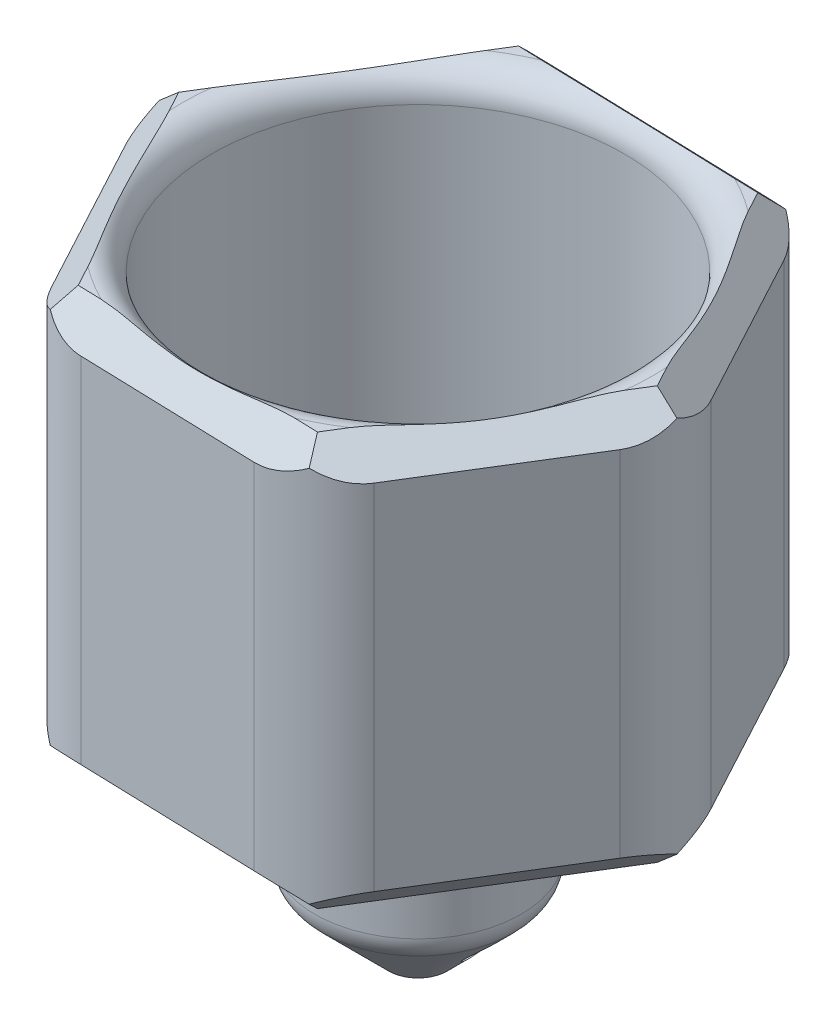
SolidWorks part; units mm, degrees
ref_plane "Front" through (0, 0, 0) normal (0, 0, 1) x (1, 0, 0)
ref_plane "Top" through (0, 0, 0) normal (0, 1, 0) x (1, 0, 0)
ref_plane "Right" through (0, 0, 0) normal (1, 0, 0) x (0, 0, -1)
sketch "Esquisse1" plane through (0, 0, 0) normal (0, 1, 0) x (1, 0, 0)
  line L1 (0.5011, 0.8102) -> (-0.451, 0.8391)
  line L2 (-0.451, 0.8391) -> (-0.9522, 0.0289)
  line L3 (-0.9522, 0.0289) -> (-0.5011, -0.8102)
  line L4 (-0.5011, -0.8102) -> (0.451, -0.8391)
  line L5 (0.451, -0.8391) -> (0.9522, -0.0289)
  line L6 (0.9522, -0.0289) -> (0.5011, 0.8102)
  circle A0 centre (0, 0) radius 0.7
  circle A1 centre (0, 0) radius 0.825 construction
  dimension "D1" = 1.4
  dimension "D2" = 1.65
extrude "Boss.-Extru.1" add sketch "Esquisse1" along normal blind 1.3
sketch "Esquisse2" plane through (0, 0, 0) normal (0, -1, 0) x (1, 0, 0)
  line L6 (0.5011, -0.8102) -> (0.9522, 0.0289)
  line L7 (0.9522, 0.0289) -> (0.451, 0.8391)
  line L8 (0.451, 0.8391) -> (-0.5011, 0.8102)
  line L9 (-0.5011, 0.8102) -> (-0.9522, -0.0289)
  line L10 (-0.9522, -0.0289) -> (-0.451, -0.8391)
  line L11 (-0.451, -0.8391) -> (0.5011, -0.8102)
  line L12 (0.5011, -0.8102) -> (0.9522, 0.0289)
  line L13 (0.9522, 0.0289) -> (0.451, 0.8391)
  line L14 (0.451, 0.8391) -> (-0.5011, 0.8102)
  line L15 (-0.5011, 0.8102) -> (-0.9522, -0.0289)
  line L16 (-0.9522, -0.0289) -> (-0.451, -0.8391)
  line L17 (-0.451, -0.8391) -> (0.5011, -0.8102)
  dimension "D1" = 0
extrude "Boss.-Extru.2" add sketch "Esquisse2" along normal blind 0.1
chamfer "Chanfrein1" distance 0.1 angle 45 12 edges at (0.0251, -0.1, -0.8246) (0.7267, -0.1, -0.3906) (0.7016, -0.1, 0.434) (-0.0251, -0.1, 0.8246) (-0.7016, -0.1, -0.434) (-0.7267, -0.1, 0.3906) (0.0251, 1.3, -0.8246) (0.7267, 1.3, -0.3906) (0.7016, 1.3, 0.434) (-0.0251, 1.3, 0.8246) (-0.7267, 1.3, 0.3906) (-0.7016, 1.3, -0.434)
fillet "Congé1" radius 0.3 6 edges at (0.5011, 0.6, -0.8102) (0.9522, 0.6, 0.0289) (0.451, 0.6, 0.8391) (-0.5011, 0.6, 0.8102) (-0.451, 0.6, -0.8391) (-0.9522, 0.6, -0.0289)
sketch "Esquisse3" plane through (0, -0.1, 0) normal (0, -1, 0) x (-1, 0, 0)
  circle A0 centre (0, 0) radius 0.35
  dimension "D1" = 0.7
extrude "Boss.-Extru.3" add sketch "Esquisse3" along normal blind 0.7
chamfer "Chanfrein2" distance 0.25 angle 45 1 edges at (0, -0.8, -0.35)
fillet "Congé2" radius 0.1 1 edges at (0, 1.3, 0.7)
fillet "Congé3" radius 0.1 1 edges at (0, -0.1, -0.35)
sketch "Esquisse4" plane through (0, 0, 0) normal (1, 0, 0) x (0, 0, -1)
  line L0 (0, -0.2) -> (0, -0.8) construction
  line L1 (0.35, -0.2) -> (-0.35, -0.2) construction
  line L2 (-0.1, -0.8) -> (0.1, -0.8) construction
  circle A0 centre (0, -0.68) radius 0.05
  dimension "D1" = 0.1
  dimension "D2" = 0.12
extrude "Enlèv. mat.-Extru.1" cut sketch "Esquisse4" against normal blind 0.7 and the other way blind 0.7
fillet "Congé4" radius 0.1 1 edges at (0, -0.55, -0.35)
sketch "Esquisse5" plane through (0, 0, 0) normal (0, 1, 0) x (1, 0, 0)
  circle A0 centre (0, 0) radius 0.225
  dimension "D1" = 0.45
extrude "Enlèv. mat.-Extru.2" cut sketch "Esquisse5" against normal blind 0.5
fillet "Congé5" radius 0.2 1 edges at (0, 0, 0.225)
scale "Echelle1" scale about origin uniform scaling yes scale factor 10
